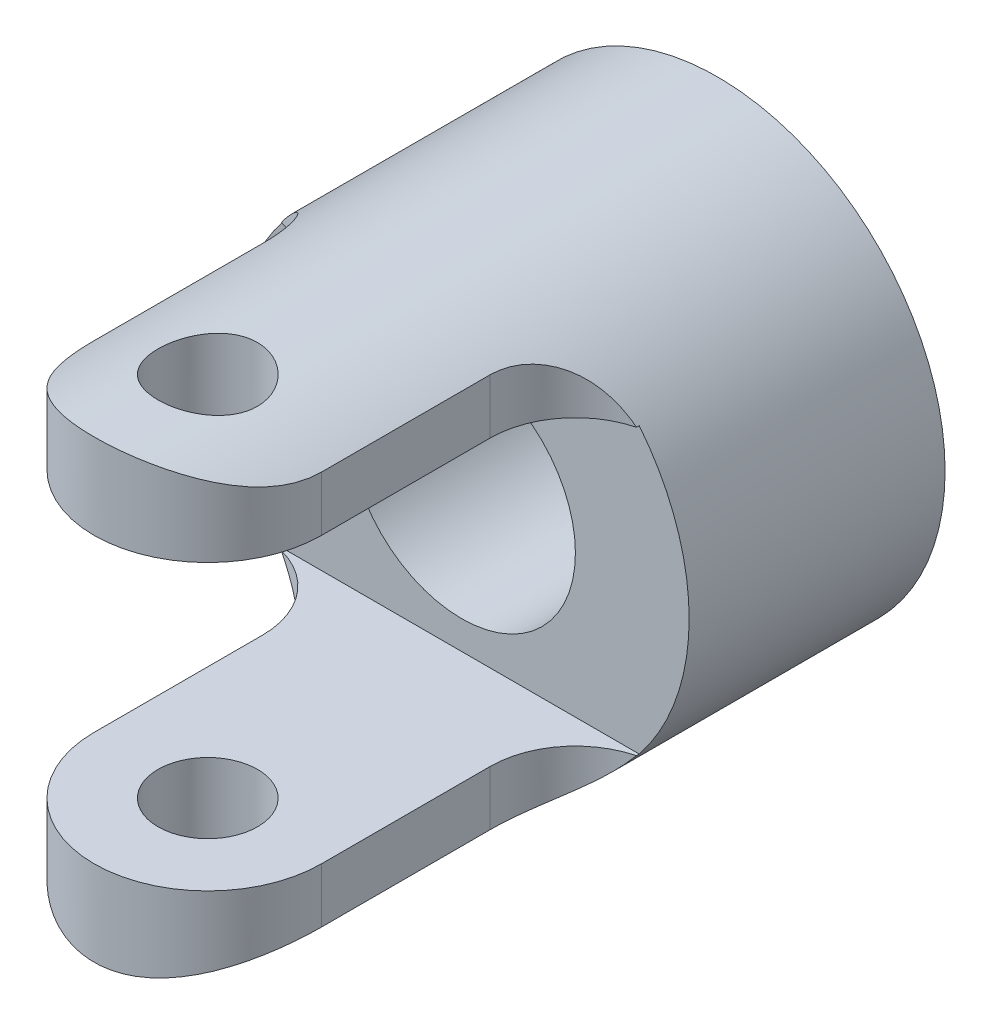
SolidWorks part; units mm, degrees
ref_plane "Front Plane" through (0, 0, 0) normal (0, 0, 1) x (1, 0, 0)
ref_plane "Top Plane" through (0, 0, 0) normal (0, 1, 0) x (1, 0, 0)
ref_plane "Right Plane" through (0, 0, 0) normal (1, 0, 0) x (0, 0, -1)
sketch "Sketch1" plane through (0, 0, 0) normal (0, 0, 1) x (1, 0, 0)
  circle A0 centre (0, 0) radius 8
  dimension "D1" = 16
extrude "Boss-Extrude1" add sketch "Sketch1" along normal blind 9
ref_plane "Plane1" through (0, 5, 0) normal (0, 1, 0) x (1, 0, 0)
sketch "Sketch2" plane through (0, 5, 0) normal (0, 1, 0) x (1, 0, 0)
  line L0 (-4, -17.9278) -> (-4, -9)
  line L1 (-8, -9) -> (8, -9) construction
  line L2 (-4, -9) -> (4, -9)
  line L3 (4, -9) -> (4, -17.9278)
  circle A0 centre (0, -17.9278) radius 1.75
  arc A1 (-4, -17.9278) -> (4, -17.9278) centre (0, -17.9278) ccw
  point P9 (0, -9)
  dimension "D1" = 3.5
  dimension "D2" = 8
  dimension "D3" = 8
extrude "Boss-Extrude2" add sketch "Sketch2" along normal up to surface (3 mm away) up to face at (8, 0, 9)
mirror "Mirror1" about plane through (0, 0, 0) normal (0, 1, 0) of "Boss-Extrude2"
sketch "Sketch3" plane through (0, 0, 0) normal (0, 0, -1) x (-1, 0, 0)
  circle A0 centre (0, 0) radius 4
  dimension "D1" = 8
extrude "Cut-Extrude1" cut sketch "Sketch3" against normal blind 10
fillet "Fillet1" radius 3 4 edges at (-4, -5.9641, 9) (4, -5.9641, 9) (4, 5.9641, 9) (-4, 5.9641, 9)
